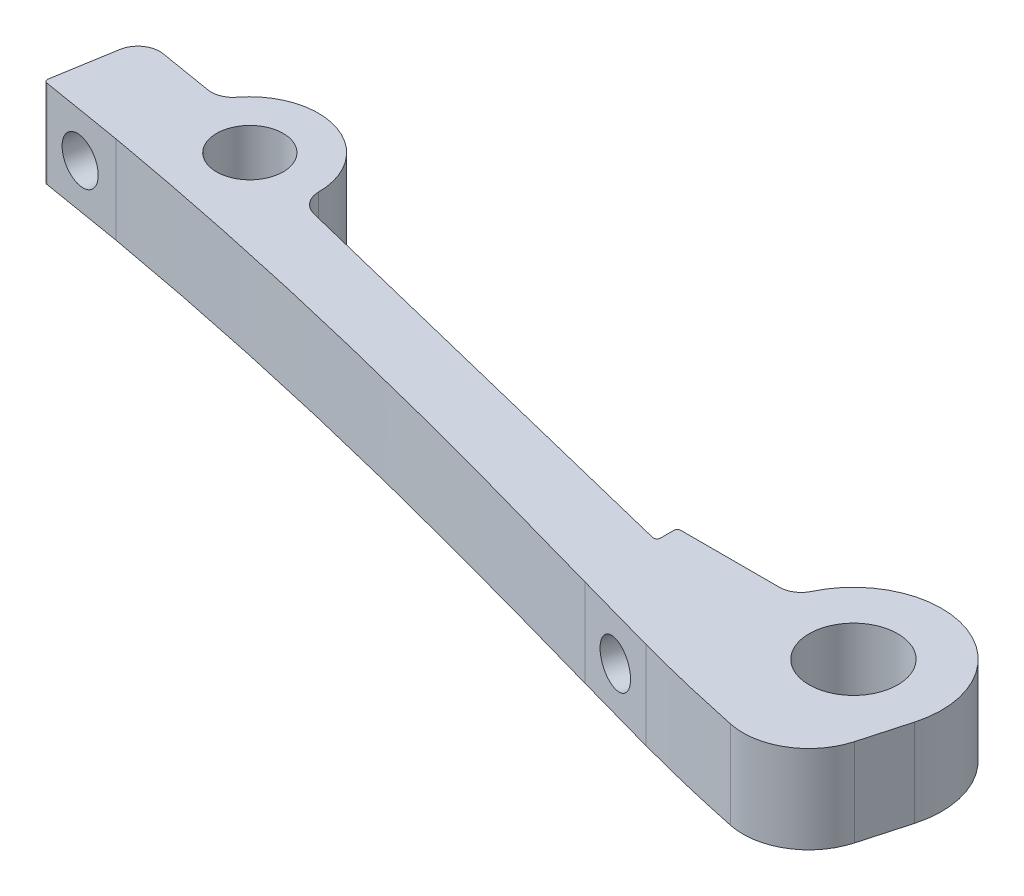
SolidWorks part; units mm, degrees
material "6061-T6 (SS)"
ref_plane "Front Plane" through (0, 0, 0) normal (0, 0, 1) x (1, 0, 0)
ref_plane "Top Plane" through (0, 0, 0) normal (0, 1, 0) x (1, 0, 0)
ref_plane "Right Plane" through (0, 0, 0) normal (1, 0, 0) x (0, 0, -1)
sketch "Sketch1" plane through (0, 0, 0) normal (0, 1, 0) x (1, 0, 0)
  line L0 (-50.8, 3.4171) -> (-63.0329, 6.8298)
  line L1 (-152.4, 28.3982) -> (-164.9278, 30.4822)
  line L2 (-302.8882, 20.0808) -> (0, 20.0808) construction
  line L3 (0, 54.0746) -> (0, -54.0746) construction
  line L4 (-237.1611, 35.2287) -> (-237.1611, 43.4682)
  line L5 (-164.9278, 30.4822) -> (-162.8439, 43.01)
  line L6 (-236.1611, 36.2359) -> (-236.1611, 42.5859)
  line L7 (-41.4276, 37.012) -> (-50.8, 3.4171)
  line L8 (-46.1138, 20.2146) -> (-46.1113, 20.2146)
  line L9 (-33.8862, -0.6152) -> (-33.8862, 33.7084) construction
  line L10 (-152.4, 28.3982) -> (-149.0337, 48.6348)
  line L11 (-141.0329, 36.363) -> (-35.4218, 10.3196)
  line L12 (-141.0329, 36.363) -> (-33.8862, 16.5466) construction
  line L14 (-149.864, 40.8508) -> (-162.8439, 43.01)
  line L17 (-63.0329, 6.8298) -> (-63.0329, 43.8426)
  line L18 (-150.316, 40.926) -> (-162.8439, 43.01) construction
  line L19 (-21.5922, 13.1168) -> (-25.8682, -2.2106)
  line L20 (-46.1138, 20.2146) -> (-63.0329, 20.2146)
  line L21 (-50.1174, 5.8637) -> (-25.5294, -0.996)
  circle A0 centre (-33.8862, 16.5466) radius 12.7635
  circle A1 centre (-33.8862, 16.5466) radius 6.4135
  circle A2 centre (-141.0329, 36.363) radius 4.826
  circle A3 centre (-141.0329, 36.363) radius 9.906
  spline S0 degree 3 poles (-236.1611, 36.2359) (-234.3302, 36.2492) (-228.1751, 36.2423) (-217.5089, 35.9478) (-204.0381, 35.1328) (-190.1739, 33.8647) (-176.0707, 32.161) (-161.8797, 30.0608) (-147.7471, 27.6111) (-133.8129, 24.8558) (-120.2041, 21.875) (-107.0398, 18.7316) (-94.4288, 15.5081) (-82.4641, 12.2836) (-71.228, 9.1472) (-60.7843, 6.194) (-51.1806, 3.4797) (-42.3494, 1.2131) (-34.2433, -0.5645) (-26.8826, -2.0412) (-20.3052, -3.2317) (-14.5777, -4.1162) (-9.769, -4.745) (-5.919, -4.9444) (-3.1012, -5.0496) (-0.9279, -4.2387) (-0.1922, -2.2877) (0.0931, -0.1154) (-0.1758, 2.5058) (-0.9682, 5.3893) (-2.328, 8.4722) (-4.2525, 11.6869) (-6.8384, 14.948) (-10.0745, 18.2281) (-13.9072, 21.5553) (-18.3404, 24.8665) (-23.3481, 28.1198) (-28.9045, 31.2809) (-34.9957, 34.2943) (-41.5837, 37.1433) (-48.6443, 39.7726) (-56.1499, 42.1442) (-64.1009, 44.1629) (-72.4989, 45.8323) (-81.386, 47.0695) (-90.7623, 47.9115) (-100.5951, 48.5335) (-110.8383, 48.8821) (-121.4297, 49.0143) (-132.3058, 48.9667) (-143.3855, 48.7883) (-154.5778, 48.4927) (-165.7881, 48.1035) (-176.9284, 47.6035) (-187.9188, 46.9903) (-198.6884, 46.2704) (-209.1689, 45.4345) (-219.2988, 44.4997) (-228.258, 43.544) (-233.8308, 42.8784) (-236.1611, 42.5859) knots 0.102282 0.102282 0.102282 0.102282 0.111022 0.131662 0.153208 0.175433 0.19811 0.221011 0.243906 0.266573 0.28881 0.310405 0.331178 0.350944 0.369556 0.386865 0.402753 0.417196 0.43038 0.442363 0.453032 0.462284 0.470026 0.476177 0.48065 0.483553 0.486421 0.489953 0.494097 0.498851 0.504197 0.510125 0.516691 0.524012 0.532092 0.540898 0.550403 0.560581 0.571396 0.582828 0.59483 0.607347 0.620384 0.633969 0.6482 0.663194 0.678899 0.695227 0.712113 0.729459 0.747143 0.76501 0.782905 0.800688 0.818242 0.835449 0.852212 0.86843 0.884009 0.89522 0.89522 0.89522 0.89522
  spline S1 degree 3 poles (-302.8882, 20.0808) (-302.8881, 20.0804) (-302.8874, 20.0804) (-302.8861, 20.0808) knots 0 0 0 0 0.000047 0.000047 0.000047 0.000047
  spline S2 degree 1 poles (-237.1611, 35.2287) (-237.1611, 43.4682) knots 0 0 1 1 construction
  spline S3 degree 3 poles (-237.1611, 35.2287) (-231.9645, 35.2662) (-221.5692, 35.1444) (-200.8027, 34.0117) (-174.9369, 31.2377) (-149.2712, 26.9713) (-128.8811, 22.7963) (-113.6599, 19.328) (-98.5087, 15.5537) (-83.4212, 11.523) (-70.883, 8.0101) (-60.8575, 5.1757) (-53.3304, 3.0479) (-45.7548, 1.0299) (-38.1125, -0.7643) (-31.7226, -2.0965) (-26.5957, -3.098) (-22.7405, -3.808) (-18.8717, -4.4649) (-15.6389, -4.9578) (-13.0465, -5.3219) (-11.0863, -5.5669) (-9.1082, -5.7601) (-7.1202, -5.8818) (-5.5134, -5.964) (-4.1374, -5.9957) (-3.0408, -5.9174) (-1.8868, -5.6698) (-0.8842, -5.2163) (-0.178, -4.5398) (0.3088, -3.7797) (0.6424, -2.8186) (0.8758, -1.7601) (1.0379, -0.3282) (0.9657, 1.4446) (0.5938, 3.4949) (-0.1787, 6.1247) (-1.572, 9.2208) (-3.7144, 12.659) (-6.2627, 15.7803) (-9.0628, 18.6207) (-12.023, 21.2626) (-16.1581, 24.5546) (-21.6052, 28.2656) (-28.4485, 32.1999) (-35.5322, 35.6562) (-42.7932, 38.7031) (-52.6732, 42.2437) (-62.8197, 44.9776) (-73.1293, 46.9327) (-80.9238, 48.0033) (-88.7393, 48.7428) (-99.1618, 49.4811) (-112.219, 49.9585) (-127.8752, 50.0298) (-148.7364, 49.7233) (-174.7963, 48.8385) (-206.0359, 46.8843) (-226.8076, 44.7679) (-237.1611, 43.4682) knots 0.10068 0.10068 0.10068 0.10068 0.125553 0.150426 0.200173 0.249919 0.274792 0.299666 0.324539 0.349412 0.374286 0.386722 0.399159 0.411595 0.424032 0.436469 0.442687 0.448905 0.455124 0.461342 0.464451 0.46756 0.47067 0.473779 0.476888 0.478442 0.479997 0.481552 0.483106 0.483883 0.484661 0.486215 0.48777 0.489324 0.492434 0.495543 0.498652 0.50487 0.511089 0.517307 0.523525 0.529744 0.535962 0.548398 0.560835 0.573272 0.585708 0.598145 0.623018 0.635455 0.647892 0.660328 0.672765 0.697638 0.722511 0.747385 0.797131 0.846878 0.896624 0.896624 0.896624 0.896624
  point P15 (0, 0)
  point P16 (-46.1113, 20.2146)
  point P25 (0, 0)
  point P26 (0, 0)
  point P29 (-33.8862, 16.5466)
  point P33 (0, 0)
  point P40 (0, 0)
  dimension "D1" = 12.7
  dimension "D2" = 50.8
  dimension "D6" = 6.35
  dimension "D7" = 9.652
  dimension "D5" = 12.827
  dimension "D13" = 2.54
  dimension "D3" = 12.7
  dimension "D4" = 152.4
  dimension "D9" = 6.35
  dimension ".1" = 5.08
  dimension "D12" = 12.7
  dimension "D10" = 1
extrude "Boss-Extrude1" add sketch "Sketch1" along normal mid plane 12.7
fillet "Fillet1" radius 3.175 4 edges at (-131.4151, 0, -33.9913) (-149.864, 0, -40.8508) (-162.8439, 0, -43.01) (-46.1113, 0, -20.2146)
fillet "Fillet4" radius 0.508 3 edges at (-164.9278, 0, -30.4822) (-63.0329, 0, -20.2146) (-63.0329, 0, -17.1285)
hole_wizard "1/4 (0.25) Diameter Hole1" positions "3DSketch2" profile "Sketch4" hole size "1/4" standard "ANSI Inch" end condition through all
sketch3d "3DSketch2"
  line L23 (-152.4, 6.35, -28.3982) -> (-152.4, -6.35, -28.3982) construction
  line L24 (-152.4, 6.35, -28.3982) -> (-164.4267, 6.35, -30.3988) construction
  line L25 (-50.8, 6.35, -3.4171) -> (-63.0329, 6.35, -6.8298) construction
  line L27 (-63.0329, 6.35, -6.8298) -> (-63.0329, -6.35, -6.8298) construction
  point P108 (-56.9164, 0, -5.1235)
  point P110 (-158.6639, 0, -29.4402)
  dimension "D1" = 6.35
  dimension "D2" = 6.35
  dimension "D3" = 6.35
  dimension "D4" = 6.35
sketch "Sketch4" plane through (-56.9164, 0, -5.1235) normal (0, 1, 0) x (0.9632, 0, 0.2687)
  line L0 (0, 0) -> (0, 49.2507)
  line L1 (0, 49.2507) -> (3.175, 49.2507)
  line L2 (3.175, 49.2507) -> (3.175, 0)
  line L5 (3.175, 0) -> (0, 0)
  line L11 (0, -6.35) -> (0, 107.95) construction
  dimension "Thru Hole Dia." = 6.35
  dimension "Thru Hole Depth" = 49.2507
fillet "Fillet8" radius 9.525 1 edges
sketch "Sketch5" plane through (0, 0, 0) normal (0, 1, 0) x (1, 0, 0)
  line L8 (-63.6625, 17.2837) -> (-128.7122, 33.3248)
  line L9 (-63.6625, 17.2837) -> (-128.7122, 33.3248)
  line L10 (-23.4933, 6.3022) -> (-21.5922, 13.1168)
  line L11 (-48.281, 20.2146) -> (-62.5249, 20.2146)
  line L12 (-63.0329, 19.7066) -> (-63.0329, 17.7769)
  line L13 (-63.0329, 6.8298) -> (-50.8, 3.4171)
  line L14 (-151.9314, 41.1947) -> (-159.7119, 42.489)
  line L15 (-163.3649, 39.878) -> (-164.8445, 30.9833)
  line L16 (-164.4267, 30.3988) -> (-152.4, 28.3982)
  line L17 (-63.0329, 6.8298) -> (-50.8, 3.4171)
  line L19 (-23.4933, 6.3022) -> (-21.5922, 13.1168)
  line L20 (-48.281, 20.2146) -> (-62.5249, 20.2146)
  line L21 (-63.0329, 19.7066) -> (-63.0329, 17.7769)
  line L23 (-151.9314, 41.1947) -> (-159.7119, 42.489)
  line L24 (-163.3649, 39.878) -> (-164.8445, 30.9833)
  line L25 (-164.4267, 30.3988) -> (-152.4, 28.3982)
  circle A0 centre (-141.0329, 36.363) radius 4.826 construction
  circle A1 centre (-33.8862, 16.5466) radius 6.4135 construction
  circle A2 centre (-141.0329, 36.363) radius 4.826
  circle A3 centre (-33.8862, 16.5466) radius 6.4135
  arc A9 (-63.6625, 17.2837) -> (-63.0329, 17.7769) centre (-63.5409, 17.7769) ccw
  arc A10 (-63.6625, 17.2837) -> (-63.0329, 17.7769) centre (-63.5409, 17.7769) ccw
  arc A11 (-131.127, 36.3966) -> (-128.7122, 33.3248) centre (-127.952, 36.4074) ccw
  arc A12 (-131.127, 36.3966) -> (-128.7122, 33.3248) centre (-127.952, 36.4074) ccw
  arc A13 (-21.5922, 13.1168) -> (-45.4135, 22.0264) centre (-33.8862, 16.5466) ccw
  arc A14 (-48.281, 20.2146) -> (-45.4135, 22.0264) centre (-48.281, 23.3896) ccw
  arc A15 (-62.5249, 20.2146) -> (-63.0329, 19.7066) centre (-62.5249, 19.7066) ccw
  arc A16 (-131.127, 36.3966) -> (-148.8916, 42.3938) centre (-141.0329, 36.363) ccw
  arc A17 (-131.127, 36.3966) -> (-148.8916, 42.3938) centre (-141.0329, 36.363) ccw
  arc A18 (-151.9314, 41.1947) -> (-148.8916, 42.3938) centre (-151.4104, 44.3267) ccw
  arc A19 (-151.9314, 41.1947) -> (-148.8916, 42.3938) centre (-151.4104, 44.3267) ccw
  arc A20 (-159.7119, 42.489) -> (-163.3649, 39.878) centre (-160.2329, 39.3571) ccw
  arc A21 (-34.6352, -0.4578) -> (-23.4933, 6.3022) centre (-32.668, 8.8618) ccw
  arc A22 (-34.6352, -0.4578) -> (-23.4933, 6.3022) centre (-32.668, 8.8618) ccw
  arc A25 (-21.5922, 13.1168) -> (-45.4135, 22.0264) centre (-33.8862, 16.5466) ccw
  arc A26 (-48.281, 20.2146) -> (-45.4135, 22.0264) centre (-48.281, 23.3896) ccw
  arc A27 (-62.5249, 20.2146) -> (-63.0329, 19.7066) centre (-62.5249, 19.7066) ccw
  arc A32 (-159.7119, 42.489) -> (-163.3649, 39.878) centre (-160.2329, 39.3571) ccw
  arc A41 (-164.8445, 30.9833) -> (-164.4267, 30.3988) centre (-164.3434, 30.8999) ccw
  arc A42 (-164.8445, 30.9833) -> (-164.4267, 30.3988) centre (-164.3434, 30.8999) ccw
  spline S1 degree 3 poles (-961.0634, -1690.8412) (-892.8698, -143.236) (-487.0426, 94.7033) (-133.8129, 24.8558) (-120.2041, 21.875) (-107.0398, 18.7316) (-94.4288, 15.5081) (-82.4641, 12.2836) (160.7037, -55.593) (392.314, -148.9602) (1140.3367, 1547.4431) knots -1.429882 -1.429882 -1.429882 -1.429882 0.243906 0.266573 0.28881 0.310405 0.331178 0.350944 0.369556 1.536333 1.536333 1.536333 1.536333 only from (-152.4, 28.3982) to (-63.0329, 6.8298)
  spline S2 degree 3 poles (-152.4, 28.3982) (-150.8358, 28.1207) (-144.6004, 26.9889) (-133.8129, 24.8558) (-120.2041, 21.875) (-107.0398, 18.7316) (-94.4288, 15.5081) (-82.4641, 12.2836) (-72.0737, 9.3833) (-65.6771, 7.5772) (-63.0329, 6.8298) knots 0.236322 0.236322 0.236322 0.236322 0.243906 0.266573 0.28881 0.310405 0.331178 0.350944 0.369556 0.382673 0.382673 0.382673 0.382673
  spline S4 degree 3 poles (-772.7427, -1844.4847) (-295.5895, 194.4359) (-82.0656, -110.3201) (239.9791, 44.3075) (-193.5845, -1980.6947) knots -0.277703 -0.277703 -0.277703 -0.277703 0.417196 1.048729 1.048729 1.048729 1.048729 only from (-50.8, 3.4171) to (-34.6352, -0.4578)
  spline S6 degree 3 poles (-50.8, 3.4171) (-47.904, 2.6388) (-42.5353, 1.2617) (-37.1234, 0.0674) (-34.6352, -0.4578) knots 0.402881 0.402881 0.402881 0.402881 0.417196 0.429334 0.429334 0.429334 0.429334
  dimension "D1" = 0
sketch3d "3DSketch3"
  circle A0 centre (-56.9164, 0, -5.1235) radius 3.175 construction
  circle A1 centre (-158.6639, 0, -29.4402) radius 3.175 construction
  circle A2 centre (-56.9164, 0, -5.1235) radius 3.175
  circle A3 centre (-158.6639, 0, -29.4402) radius 3.175
  point P2 (-57.7696, 0, -2.0653)
  point P5 (-159.1849, 0, -26.3082)
  point P7 (-57.7696, 0, -2.0653)
  point P9 (-159.1849, 0, -26.3082)
